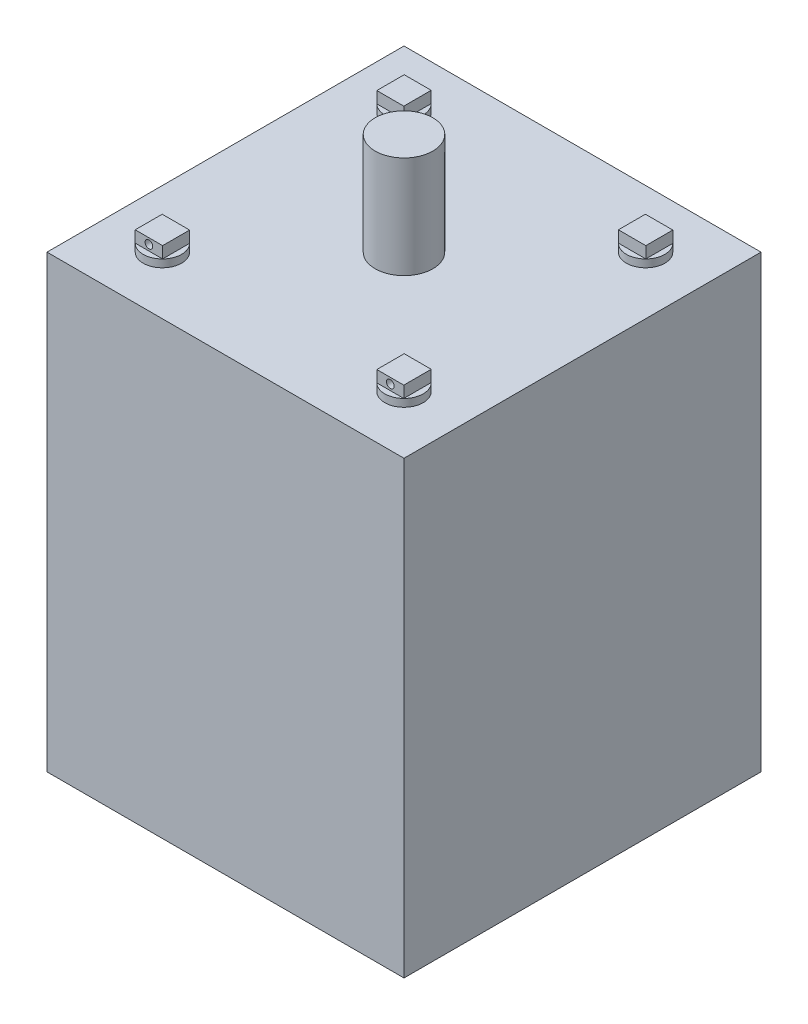
SolidWorks part; units mm, degrees
ref_plane "Front Plane" through (0, 0, 0) normal (0, 0, 1) x (1, 0, 0)
ref_plane "Top Plane" through (0, 0, 0) normal (0, 1, 0) x (1, 0, 0)
ref_plane "Right Plane" through (0, 0, 0) normal (1, 0, 0) x (0, 0, -1)
sketch "Sketch1" plane through (0, 0, 0) normal (0, 1, 0) x (1, 0, 0)
  line L1 (0, 0) -> (92.8, 0)
  line L2 (0, 0) -> (0, 92.8)
  line L3 (0, 92.8) -> (92.8, 92.8)
  line L4 (92.8, 0) -> (92.8, 92.8)
  dimension "D1" = 92.8
extrude "Boss-Extrude1" add sketch "Sketch1" along normal blind 117
sketch "Sketch2" plane through (0, 117, 0) normal (0, 1, 0) x (1, 0, 0)
  line L0 (46.4, 0) -> (46.4, 92.8) construction
  line L4 (0, 92.8) -> (0, 0)
  line L5 (0, 0) -> (92.8, 0)
  line L6 (92.8, 0) -> (92.8, 92.8)
  line L7 (92.8, 92.8) -> (0, 92.8)
  line L8 (0, 92.8) -> (0, 0)
  line L9 (0, 0) -> (92.8, 0)
  line L10 (92.8, 0) -> (92.8, 92.8)
  line L11 (92.8, 92.8) -> (0, 92.8)
  circle A0 centre (46.4, 46.4) radius 7.5
  dimension "D1" = 0
extrude "Boss-Extrude2" add sketch "Sketch2" along normal blind 143.5 from surface contours A0 starting at face at (46.4, 0, -46.4)
sketch "Sketch3" plane through (0, 117, 0) normal (0, 1, 0) x (1, 0, 0)
  line L0 (77.8, 77.8) -> (15, 77.8)
  line L1 (15, 77.8) -> (15, 15)
  line L2 (15, 15) -> (77.8, 15)
  line L3 (77.8, 15) -> (77.8, 77.8)
  line L4 (0, 92.8) -> (0, 0)
  line L5 (0, 0) -> (92.8, 0)
  line L6 (92.8, 0) -> (92.8, 92.8)
  line L7 (92.8, 92.8) -> (0, 92.8)
  line L8 (0, 92.8) -> (0, 0)
  line L9 (0, 0) -> (92.8, 0)
  line L10 (92.8, 0) -> (92.8, 92.8)
  line L11 (92.8, 92.8) -> (0, 92.8)
  circle A0 centre (15, 77.8) radius 5
  dimension "D1" = 0
  dimension "D2" = 15
extrude "Boss-Extrude3" add sketch "Sketch3" along normal blind 2 contours L0 A0 L1 | L1 A0 L0 region at (17.1221, 117, -75.6779) region at (14.2926, 117, -78.5074)
sketch "Sketch4" plane through (0, 119, 0) normal (0, 1, 0) x (1, 0, 0)
  line L1 (18.5089, 81.3619) -> (11.4911, 81.3619)
  line L2 (18.5089, 81.3619) -> (18.5089, 74.2381)
  line L3 (18.5089, 74.2381) -> (11.4911, 74.2381)
  line L4 (11.4911, 81.3619) -> (11.4911, 74.2381)
  line L5 (18.5089, 81.3619) -> (11.4911, 74.2381) construction
  line L6 (18.5089, 74.2381) -> (11.4911, 81.3619) construction
  circle A1 centre (15, 77.8) radius 5
  circle A2 centre (15, 77.8) radius 5
  dimension "D1" = 0
extrude "Boss-Extrude4" add sketch "Sketch4" along normal blind 3 contours L1 L4 L3 L2 region at (15, 119, -77.8)
sketch "Sketch5" plane through (0, 0, -81.3619) normal (0, 0, -1) x (-1, 0, 0)
  line L0 (-18.5089, 120.5) -> (-11.4911, 120.5) construction
  line L4 (-18.5089, 119) -> (-11.4911, 119)
  line L5 (-11.4911, 119) -> (-11.4911, 122)
  line L6 (-11.4911, 122) -> (-18.5089, 122)
  line L7 (-18.5089, 122) -> (-18.5089, 119)
  line L8 (-18.5089, 119) -> (-11.4911, 119)
  line L9 (-11.4911, 119) -> (-11.4911, 122)
  line L10 (-11.4911, 122) -> (-18.5089, 122)
  line L11 (-18.5089, 122) -> (-18.5089, 119)
  circle A0 centre (-15, 120.5) radius 1
  dimension "D1" = 0
extrude "Cut-Extrude1" cut sketch "Sketch5" against normal blind 3.5 contours A0
pattern_circular "CirPattern1" count 4 over 360 about axis through (46.4, 143.5, -46.4) along (0, -1, 0) of "Boss-Extrude4", "Boss-Extrude3"
ref_plane "Plane1" through (0, 0, -46.4) normal (0, 0, -1) x (-1, 0, 0)
ref_plane "Plane2" through (46.4, 0, 0) normal (1, 0, 0) x (0, 0, -1)
mirror "Mirror1" about plane through (0, 0, -46.4) normal (0, 0, -1) of "Cut-Extrude1"
mirror "Mirror2" about plane through (46.4, 0, 0) normal (1, 0, 0) of "Cut-Extrude1" second plane through (0, 0, -46.4) second plane normal (0, 0, -1)
